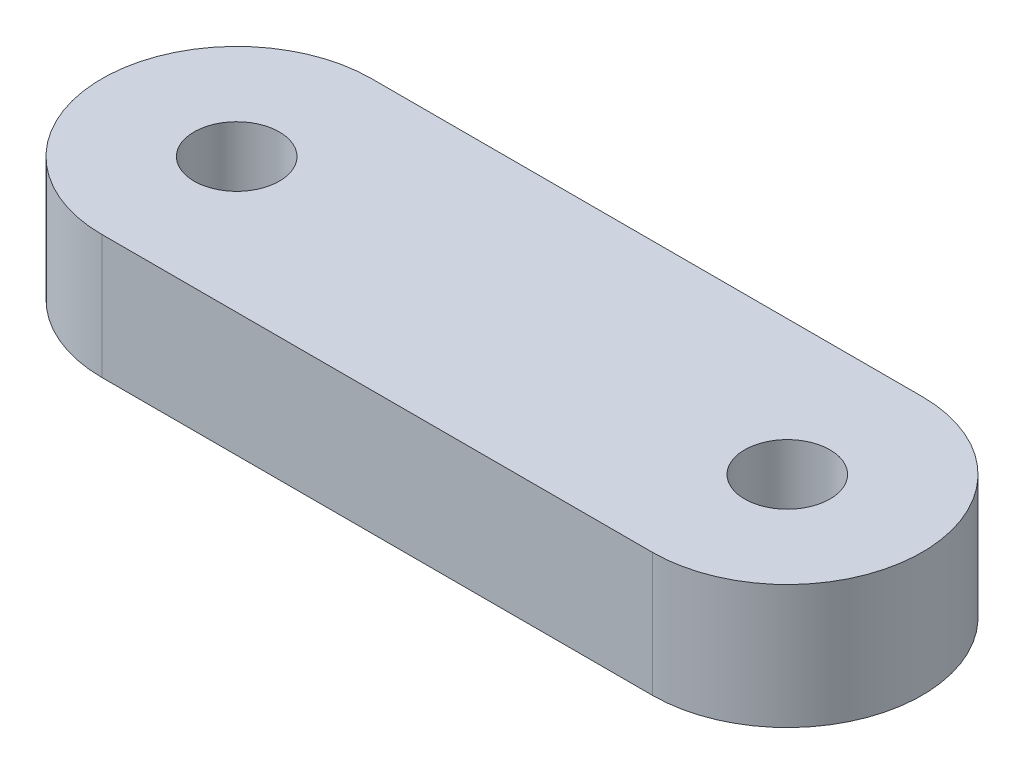
SolidWorks part; units mm, degrees
ref_plane "Front Plane" through (0, 0, 0) normal (0, 0, 1) x (1, 0, 0)
ref_plane "Top Plane" through (0, 0, 0) normal (0, 1, 0) x (1, 0, 0)
ref_plane "Right Plane" through (0, 0, 0) normal (1, 0, 0) x (0, 0, -1)
sketch "Sketch1" plane through (0, 0, 0) normal (0, 1, 0) x (1, 0, 0)
  line L0 (14.9, 0) -> (14.9, 15.5804) construction
  line L1 (-10, 4.9) -> (10, 4.9)
  line L2 (-14.9, 0) -> (-14.9, 15.5804) construction
  line L3 (-10, -4.9) -> (10, -4.9)
  line L4 (-10, 4.9) -> (-10, -4.9) construction
  line L5 (-10, 4.9) -> (10, -4.9) construction
  line L6 (-10, -4.9) -> (10, 4.9) construction
  line L7 (10, 4.9) -> (10, -4.9) construction
  line L8 (0, 4.9) -> (0, -4.9) construction
  arc A0 (-10, 4.9) -> (-10, -4.9) centre (-10, 0) ccw
  arc A1 (10, -4.9) -> (10, 4.9) centre (10, 0) ccw
  circle A2 centre (-10, 0) radius 1.55
  circle A3 centre (10, 0) radius 1.55
  point P0 (0, 0)
  dimension "D4" = 4.9
  dimension "D5" = 3.1
  dimension "D1" = 9.8
  dimension "D2" = 20
extrude "Boss-Extrude1" add sketch "Sketch1" along normal blind 4.5
equation "\"Y-ROD-SPACING\"=75"
equation "\"Y-BED-OFFSET\"=2"
equation "\"Y-BED-ROD-INSET\"=3.5"
equation "\"T-SLOT-NUT-FILLET-RADIUS\"=0.25"
equation "\"T-SLOT-SCREW-SHAFT-RADIUS\"=1.75"
equation "\"T-SLOT-SCREW-SHAFT-CUTOUT-LENGTH\"=10.5"
equation "\"T-SLOT-NUT-DEPTH\"=4.2"
equation "\"T-SLOT-NUT-WIDTH\"=3"
equation "\"T-SLOT-NUT-END-DISTANCE\"=8"
equation "\"ACRYLIC-TAB-CUTOUT-SIZE\"=\"ACRYLIC-THICKNESS\"+\"ACRYLIC-TAB-TOLERANCE\"*2"
equation "\"ACRYLIC-M3-HOLE\"=3.1"
equation "\"D5@Sketch1\"=\"ACRYLIC-M3-HOLE\""
equation "\"SMOOTHROD-CAP-SCREW-DISTANCE\"=20"
equation "\"D2@Sketch1\"=\"SMOOTHROD-CAP-SCREW-DISTANCE\""
equation "\"X-ROD-SPACING\"=45"
equation "\"Z-ROD-SPACING\"=17.5"
equation "\"ACRYLIC-THICKNESS\"=10"
equation "\"ACRYLIC-THICKNESS2\"=4.5"
equation "\"ACRYLIC-TAB-WIDTH\"=\"ACRYLIC-THICKNESS\""
equation "\"FRAME-WIDTH-INNER\"=370"
equation "\"NEMA17-HOLE-SPACING\"=31"
equation "\"NEMA17-CENTRAL-CUTOUT\"=22.5"
equation "\"Z-BRACKET-REACH\"=55"
equation "\"TOP-BRACKET-SPACING\"=40"
equation "\"SMOOTHROD-X-LENGTH\"=350"
equation "\"SMOOTHROD-Y-LENGTH\"=350"
equation "\"SMOOTHROD-Z-LENGTH\"=350"
equation "\"SMOOTHROD-TIGHTENING-HEADROOM\"=.25"
equation "\"LEADSCREW-Z-LENGTH\"=300"
equation "\"SCREW-LENGTH-FRAME\"=\"ACRYLIC-THICKNESS\" + 10"
equation "\"SCREW-HEAD-RADIUS\"=6"
equation "\"PRINTED-X-SMOOTHROD-DIAMETER\"=8.2"
equation "\"PRINTED-X-SMOOTHROD-CUTOUT\"=10"
equation "\"PRINTED-X-BASE-HEIGHT\"=10"
equation "\"PRINTED-LM8UU-CUTOUT-SIZE\"=15.25"
equation "\"PRINTED-LM8UU-CUTOUT-LENGTH\"=24.5"
equation "\"PRINTED-X-IDLER-HEIGHT\"=16"
equation "\"PSU-MOUNTING-WIDTH\"=95"
equation "\"PSU-MOUNTING-HEIGHT\"=177"
equation "\"D1@Boss-Extrude1\"=\"ACRYLIC-THICKNESS2\""
